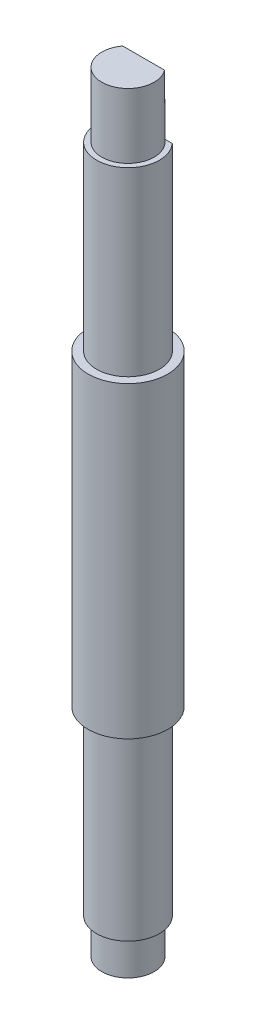
SolidWorks part; units mm, degrees
ref_plane "前视基准面" through (0, 0, 0) normal (0, 0, 1) x (1, 0, 0)
ref_plane "上视基准面" through (0, 0, 0) normal (0, 1, 0) x (1, 0, 0)
ref_plane "右视基准面" through (0, 0, 0) normal (1, 0, 0) x (0, 0, -1)
sketch "草图1" plane through (0, 0, 0) normal (0, 0, 1) x (1, 0, 0)
  line L0 (0, 5.9553) -> (0, -34.75)
  line L1 (1.25, 5.9553) -> (1.25, 2.8553)
  line L2 (1.5, 2.8553) -> (1.25, 2.8553)
  line L3 (1.5, 2.8553) -> (1.5, -5.7947)
  line L4 (1.5, -5.7947) -> (1.9, -5.7947)
  line L5 (1.9, -5.7947) -> (1.9, -20.4947)
  line L6 (1.25, -30.8447) -> (0, -30.8447)
  line L9 (1.25, 5.9553) -> (0, 5.9553)
  line L10 (1.5, -29.1447) -> (1.25, -29.1447)
  line L11 (1.25, -29.1447) -> (1.25, -30.8447)
  line L12 (1.9, -20.4947) -> (1.5, -20.4947)
  line L13 (1.5, -20.4947) -> (1.5, -29.1447)
  dimension "D2" = 1.5
  dimension "D3" = 1.25
  dimension "D4" = 3.1
  dimension "D5" = 36.8
  dimension "D6" = 1.7
  dimension "D8" = 11.75
  dimension "D9" = 10.35
  dimension "D10" = 1.25
  dimension "D11" = 1.9
revolve "旋转2" add sketch "草图1" angle 360 about L0 region at (0.8308, -12.607, 0)
ref_plane "基准面1" through (0, 3.4553, 0) normal (0, 1, 0) x (1, 0, 0)
sketch "草图5" plane through (0, 5.9553, 0) normal (0, 1, 0) x (1, 0, 0)
  line L0 (-1.118, 1) -> (1.118, 1)
  arc A0 (1.118, 1) -> (-1.118, 1) centre (0, 0) ccw
  dimension "D1" = 3
  dimension "D2" = 1
extrude "切除-拉伸3" cut sketch "草图5" against normal up to surface (11.75 mm away) up to face at (-1.9, -5.7947, 0)
sketch "草图7" plane through (0, -30.8447, 0) normal (0, -1, 0) x (1, 0, 0)
  line L0 (-1.118, -1) -> (1.118, -1) construction
  line L1 (-1.118, -1) -> (1.118, -1)
  circle A0 centre (0, 0) radius 1.5 construction
  circle A1 centre (0, 0) radius 1.5
  circle M1 centre (0, 0) radius 1.25
extrude "切除-拉伸5" cut sketch "草图7" against normal up to surface (10.35 mm away) contours L1 A1 M1 | L1 M1 region at (0, -30.8447, -1.2535) region at (0, -30.8447, -1.1009) up to face at (-1.5, -20.4947, 0)
sketch "草图8" plane through (0, -30.8447, 0) normal (0, -1, 0) x (1, 0, 0)
  circle A0 centre (0, 0) radius 0.7
  dimension "D1" = 1.4
sketch "草图10" plane through (0, 5.9553, 0) normal (0, 1, 0) x (1, 0, 0)
  line L0 (-1, 0.75) -> (1, 0.75)
  arc A0 (-0.75, 1) -> (0.75, 1) centre (0, 0) ccw construction
  arc A1 (1, 0.75) -> (-1, 0.75) centre (0, 0) ccw
  dimension "D1" = 0.75
extrude "切除-拉伸7" cut sketch "草图10" against normal blind 1.4
ref_plane "基准面2" through (0, -1.4697, 0) normal (0, 1, 0) x (1, 0, 0)
ref_axis "基准轴1" through (0, -5.7947, 0) along (0, 1, 0)
ref_point "点1"
